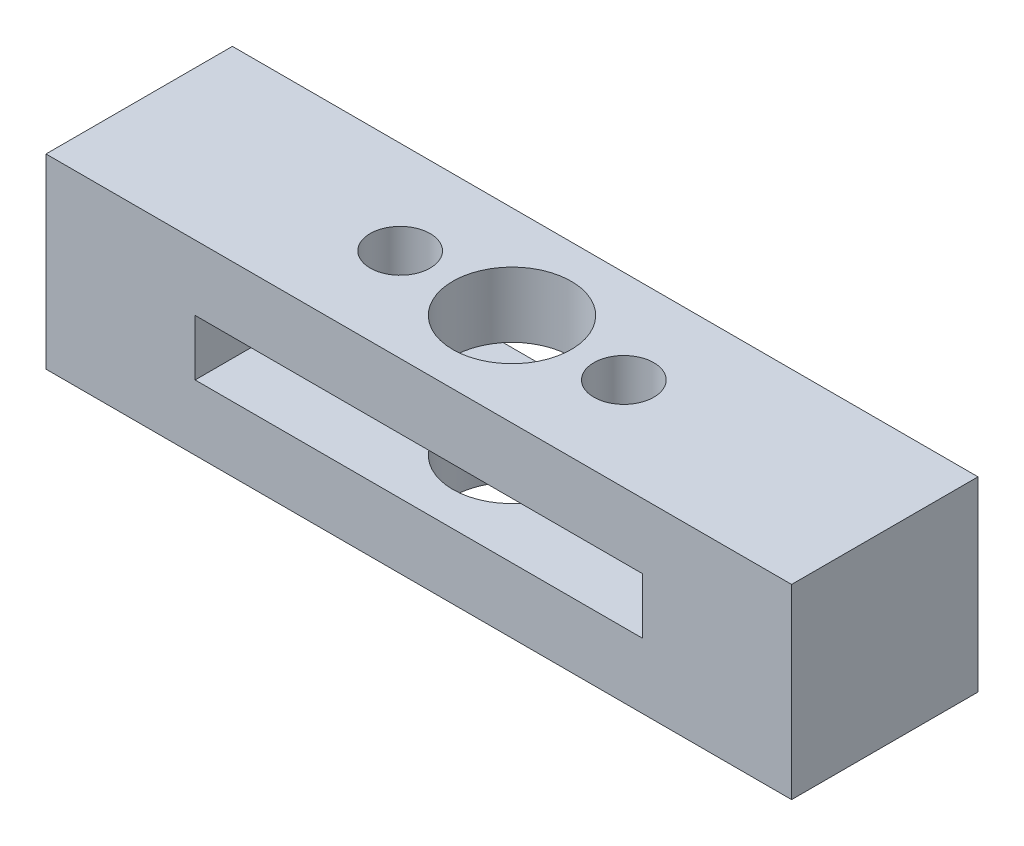
SolidWorks part; units mm, degrees
ref_plane "Front" through (0, 0, 0) normal (0, 0, 1) x (1, 0, 0)
ref_plane "Top" through (0, 0, 0) normal (0, 1, 0) x (1, 0, 0)
ref_plane "Right" through (0, 0, 0) normal (1, 0, 0) x (0, 0, -1)
sketch "Sketch1" plane through (0, 0, 0) normal (0, 0, 1) x (1, 0, 0)
  line L1 (31.75, -7.9375) -> (-31.75, -7.9375)
  line L2 (31.75, -7.9375) -> (31.75, 7.9375)
  line L3 (31.75, 7.9375) -> (-31.75, 7.9375)
  line L4 (-31.75, -7.9375) -> (-31.75, 7.9375)
  line L5 (31.75, -7.9375) -> (-31.75, 7.9375) construction
  line L6 (31.75, 7.9375) -> (-31.75, -7.9375) construction
  line L7 (19.05, -2.3812) -> (-19.05, -2.3813)
  line L8 (19.05, -2.3812) -> (19.05, 2.3813)
  line L9 (19.05, 2.3813) -> (-19.05, 2.3812)
  line L10 (-19.05, -2.3813) -> (-19.05, 2.3812)
  line L11 (19.05, -2.3812) -> (-19.05, 2.3812) construction
  line L12 (19.05, 2.3813) -> (-19.05, -2.3813) construction
  point P0 (0, 0)
  point P6 (0, 0)
  dimension "D1" = 15.875
  dimension "D2" = 38.1
  dimension "D3" = 63.5
  dimension "D4" = 4.7625
extrude "Boss-Extrude1" add sketch "Sketch1" along normal mid plane 15.875
hole_wizard "1/4-20 Tapped Hole1" positions "Sketch2" profile "Sketch3" tap size "1/4-20" standard "ANSI Inch" end condition through all
sketch "Sketch2" plane through (0, 7.9375, 0) normal (0, 1, 0) x (1, 0, 0)
  line L1 (0, 0) -> (0, 17.4866) construction
  line L3 (31.75, -7.9375) -> (-31.75, -7.9375) construction
  point P0 (9.525, 0)
  point P2 (-9.525, 0)
  dimension "D1" = 19.05
  dimension "D2" = 7.9375
sketch "Sketch3" plane through (9.525, 7.9375, 0) normal (1, 0, 0) x (0, 0, 1)
  line L0 (0, 0) -> (0, 15.875)
  line L1 (0, 15.875) -> (2.5527, 15.875)
  line L2 (2.5527, 15.875) -> (2.5527, 0)
  line L5 (2.5527, 0) -> (0, 0)
  line L11 (0, -6.35) -> (0, 107.95) construction
  dimension "Thru Tap Drill Dia." = 5.1054
  dimension "Thru Tap Drill Depth" = 15.875
cosmetic thread "Hole Thread1" parameters "D2"=6.35
cosmetic thread "Hole Thread2" parameters "D2"=6.35
hole_wizard "3/8 Clearance Hole1" positions "Sketch4" profile "Sketch5" hole size "3/8" standard "ANSI Inch" end condition through all
sketch "Sketch4" plane through (0, 7.9375, 0) normal (0, 1, 0) x (1, 0, 0)
  point P0 (0, 0)
sketch "Sketch5" plane through (0, 7.9375, 0) normal (1, 0, 0) x (0, 0, 1)
  line L0 (0, 0) -> (0, 15.875)
  line L1 (0, 15.875) -> (5.0419, 15.875)
  line L2 (5.0419, 15.875) -> (5.0419, 0)
  line L5 (5.0419, 0) -> (0, 0)
  line L11 (0, -6.35) -> (0, 107.95) construction
  dimension "Thru Hole Dia." = 10.0838
  dimension "Thru Hole Depth" = 15.875
